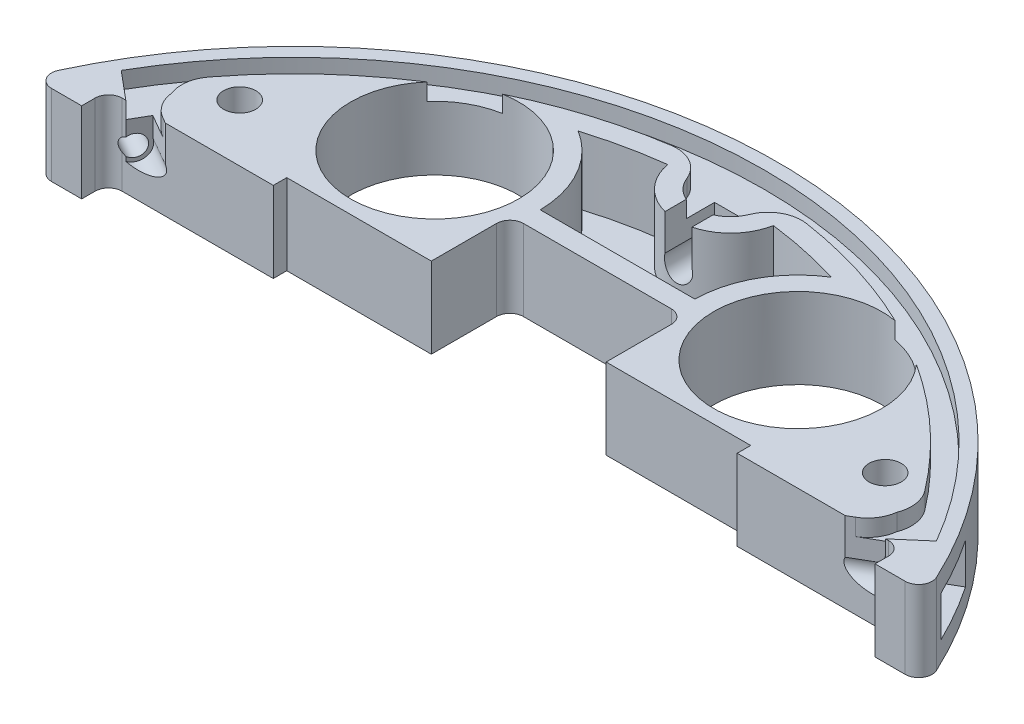
SolidWorks part; units mm, degrees
material "ABS"
ref_plane "Front Plane" through (0, 0, 0) normal (0, 0, 1) x (1, 0, 0)
ref_plane "Top Plane" through (0, 0, 0) normal (0, 1, 0) x (1, 0, 0)
ref_plane "Right Plane" through (0, 0, 0) normal (1, 0, 0) x (0, 0, -1)
sketch "Sketch1" plane through (0, 0, 0) normal (0, 1, 0) x (1, 0, 0)
  line L0 (0, -85) -> (-32.2211, -64.3879) construction
  line L1 (0, -85) -> (0, 0) construction
  arc A0 (36.2245, -62.2237) -> (-36.2245, -62.2237) centre (0, 0) ccw
  arc A1 (29.8119, -61.0352) -> (-29.8119, -61.0352) centre (0, -85) ccw
  arc A2 (36.2245, -62.2237) -> (29.8119, -61.0352) centre (33.7089, -57.9026) cw
  arc A3 (-29.8119, -61.0352) -> (-36.2245, -62.2237) centre (-33.7089, -57.9026) cw
  dimension "D1" = 144
  dimension "D2" = 76.5
  dimension "D4" = 5
  dimension "D3" = 85
extrude "Boss-Extrude1" add sketch "Sketch1" along normal mid plane 12
sketch "solenoid placement" plane through (0, 6, 0) normal (0, 1, 0) x (1, 0, 0)
  line L0 (0, 0) -> (0, -36) construction
  line L5 (-19, -36) -> (19, -36)
  line L7 (19, -36) -> (19, 28)
  line L9 (19, 28) -> (-19, 28)
  line L11 (-19, 28) -> (-19, -36)
  circle A1 centre (0, 0) radius 72 construction
  arc A2 (36.2245, -62.2237) -> (-36.2245, -62.2237) centre (0, 0) ccw construction
  dimension "D1" = 36
  dimension "D2" = 64
  dimension "D3" = 38
extrude "Cut-Extrude1" cut sketch "solenoid placement" against normal through all
sketch "Sketch4" plane through (0, 6, 0) normal (0, 1, 0) x (1, 0, 0)
  line L1 (-13, 28) -> (13, 28)
  line L2 (-13, 28) -> (-13, 43.2)
  line L4 (13, 28) -> (13, 43.2)
  line L5 (11, 45.2) -> (-11, 45.2)
  line L6 (19, 28) -> (-19, 28) construction
  arc A0 (11, 45.2) -> (13, 43.2) centre (11, 43.2) cw
  arc A1 (-11, 45.2) -> (-13, 43.2) centre (-11, 43.2) ccw
  point P6 (0, 28)
  dimension "D1" = 2
  dimension "D2" = 26
  dimension "D3" = 17.2
extrude "Cut-Extrude4" cut sketch "Sketch4" against normal through all
sketch "Sketch5" plane through (0, 6, 0) normal (0, 1, 0) x (1, 0, 0)
  line L0 (0, 0) -> (0, 72) construction
  arc A0 (36.2245, -62.2237) -> (-36.2245, -62.2237) centre (0, 0) ccw construction
  circle A1 centre (27, 48) radius 12.5
  circle A3 centre (-27, 48) radius 12.5
  dimension "D3" = 25
  dimension "D1" = 27
  dimension "D2" = 48
extrude "Cut-Extrude5" cut sketch "Sketch5" against normal through all
sketch "Sketch6" plane through (0, 6, 0) normal (0, 1, 0) x (1, 0, 0)
  line L0 (0, 0) -> (0, 72) construction
  arc A0 (36.2245, -62.2237) -> (-36.2245, -62.2237) centre (0, 0) ccw construction
  circle A1 centre (48, 40) radius 2.4
  circle A6 centre (-48, 40) radius 2.4
  dimension "D3" = 4.8
  dimension "D1" = 48
  dimension "D2" = 40
extrude "Cut-Extrude6" cut sketch "Sketch6" against normal through all
sketch "Sketch3" plane through (0, 6, 0) normal (0, 1, 0) x (1, 0, 0)
  line L1 (-72, -31.5) -> (72, -31.5) construction
  line L2 (-72, -31.5) -> (-72, 27.5)
  line L3 (-59, 31.5) -> (0, 31.5)
  line L4 (72, -31.5) -> (72, 27.5)
  line L5 (0, -31.5) -> (0, 31.5) construction
  line L6 (72, 27.5) -> (59, 27.5)
  line L9 (0, 31.5) -> (59, 31.5)
  line L10 (-72, -31.5) -> (-72, -101.6464)
  line L11 (72, -31.5) -> (72, -101.6464)
  line L12 (72, -101.6464) -> (-72, -101.6464)
  line L13 (59, 27.5) -> (59, 31.5)
  line L14 (-59, 27.5) -> (-59, 31.5)
  line L15 (-72, 27.5) -> (-59, 27.5)
  arc A0 (36.2245, -62.2237) -> (-36.2245, -62.2237) centre (0, 0) ccw construction
  point P0 (0, 0)
  dimension "D2" = 13
  dimension "D1" = 63
  dimension "D3" = 4
extrude "Cut-Extrude3" cut sketch "Sketch3" against normal through all
sketch "Sketch7" plane through (0, 0, 0) normal (0, 1, 0) x (1, 0, 0)
  line L0 (0, 0) -> (62.3538, 36) construction
  line L1 (0, 0) -> (-62.3538, 36) construction
  line L2 (0, 0) -> (0, 72) construction
  arc A0 (0, 72) -> (62.3538, 36) centre (0, 0) cw construction
  arc A1 (0, 72) -> (-62.3538, 36) centre (0, 0) ccw construction
  arc A2 (66.5413, 27.5) -> (-66.5413, 27.5) centre (0, 0) ccw construction
  dimension "D1" = 120
fillet "Fillet1" radius 2 4 edges at (-66.5413, 0, -27.5) (-59, 0, -31.5) (59, 0, -31.5) (66.5413, 0, -27.5)
sketch "Sketch8" plane through (0, 0, 0) normal (0, 1, 0) x (1, 0, 0)
  line L0 (5, 71.8262) -> (5, 68.8262)
  line L1 (0, 0) -> (64.7033, 31.583) construction
  line L2 (64.7033, 31.583) -> (59.7033, 40.2432) construction
  line L3 (64.7033, 31.583) -> (62.1052, 30.083)
  line L4 (62.1052, 30.083) -> (57.1052, 38.7432)
  line L5 (59.7033, 40.2432) -> (57.1052, 38.7432)
  line L6 (0, 0) -> (59.7033, 40.2432) construction
  line L7 (5, 68.8262) -> (-5, 68.8262)
  line L8 (-5, 71.8262) -> (-5, 68.8262)
  line L9 (5, 71.8262) -> (-5, 71.8262) construction
  line L10 (-59.7033, 40.2432) -> (-57.1052, 38.7432)
  line L11 (-57.1052, 38.7432) -> (-62.1052, 30.083)
  line L12 (-64.7033, 31.583) -> (-62.1052, 30.083)
  line L13 (-59.7033, 40.2432) -> (-64.7033, 31.583) construction
  arc A0 (59.7033, 40.2432) -> (64.7033, 31.583) centre (0, 0) cw
  arc A2 (-5, 71.8262) -> (5, 71.8262) centre (0, 0) cw
  arc A3 (-64.7033, 31.583) -> (-59.7033, 40.2432) centre (0, 0) cw
  point P4 (62.3538, 36)
  point P10 (-62.3538, 36)
  point P18 (0, 0)
  dimension "D1" = 10
  dimension "D2" = 3
extrude "Cut-Extrude7" cut sketch "Sketch8" against normal mid plane 6
sketch "Sketch10" plane through (0, 6, 0) normal (0, 1, 0) x (1, 0, 0)
  line L0 (0, 0) -> (0, 65) construction
  circle A0 centre (0, 65) radius 5
  dimension "D2" = 10
  dimension "D1" = 65
extrude "Cut-Extrude9" cut sketch "Sketch10" against normal blind 2.5
sketch "Sketch11" plane through (0, 6, 0) normal (0, 1, 0) x (1, 0, 0)
  line L1 (34.5, -33.5) -> (-34.5, -33.5)
  line L2 (34.5, -33.5) -> (34.5, 33.5)
  line L3 (34.5, 33.5) -> (-34.5, 33.5)
  line L4 (-34.5, -33.5) -> (-34.5, 33.5)
  line L5 (34.5, -33.5) -> (-34.5, 33.5) construction
  line L6 (34.5, 33.5) -> (-34.5, -33.5) construction
  point P0 (0, 0)
  dimension "D1" = 67
  dimension "D2" = 69
extrude "Cut-Extrude10" cut sketch "Sketch11" against normal through all
sketch "Sketch13" plane through (-59.6052, 0, -34.4131) normal (-0.866, 0, -0.5) x (-0.5, 0, 0.866)
  circle A0 centre (0, 0) radius 1.55
  dimension "D1" = 3.1
extrude "Cut-Extrude11" cut sketch "Sketch13" against normal blind 4.2
sketch "Sketch14" plane through (-55.9679, 0, -32.3131) normal (-0.866, 0, -0.5) x (-0.5, 0, 0.866)
  circle A0 centre (0, 0) radius 2.1
  dimension "D1" = 4.2
extrude "Cut-Extrude12" cut sketch "Sketch14" against normal blind 9
sketch "Sketch15" plane through (-55.9679, 0, -32.3131) normal (0.866, 0, 0.5) x (0.5, 0, -0.866)
  line L1 (-2, 0) -> (2, 0)
  line L2 (-2, 0) -> (-2, 10.8827)
  line L3 (-2, 10.8827) -> (2, 10.8827)
  line L4 (2, 0) -> (2, 10.8827)
  point P0 (0, 0)
  dimension "D1" = 4
extrude "Cut-Extrude13" cut sketch "Sketch15" along normal blind 9
pattern_circular "CirPattern1" count 3 over 120 about axis through (0, 6, 0) along (0, -1, 0) of "Cut-Extrude11", "Cut-Extrude12", "Cut-Extrude13"
sketch "Sketch16" plane through (0, 6, 0) normal (0, 1, 0) x (1, 0, 0)
  line L0 (0, 0) -> (-62.3538, 36) construction
  line L1 (0, 0) -> (62.3538, 36) construction
  line L2 (-56.4374, 31.5) -> (-54.9679, 34.0451) construction
  line L4 (-56.4374, 31.5) -> (-60.6218, 35)
  line L5 (3.5, 65) -> (-3.5, 65)
  line L6 (3.5, 65) -> (3.5, 66.9085)
  line L7 (-53.9374, 35.8301) -> (-55.6706, 37.2799)
  line L8 (-3.5, 65) -> (-3.5, 66.9085)
  line L9 (56.4775, 31.4305) -> (60.6218, 35)
  line L10 (53.9775, 35.7607) -> (55.6964, 37.2412)
  line L12 (54.9679, 34.0451) -> (56.4374, 31.5) construction
  line L13 (-53.9374, 35.8301) -> (-56.4374, 31.5)
  line L14 (53.9775, 35.7607) -> (56.4775, 31.4305)
  arc A0 (60.6218, 35) -> (-60.6218, 35) centre (0, 0) ccw
  arc A1 (55.6964, 37.2412) -> (3.5, 66.9085) centre (0, 0) ccw
  arc A2 (2, 60.4174) -> (-2, 60.4174) centre (0, 65) ccw construction
  arc A3 (-3.5, 66.9085) -> (-55.6706, 37.2799) centre (0, 0) ccw
  arc A4 (59, 29.5) -> (57, 31.5) centre (57, 29.5) ccw construction
  point P15 (0, 65)
  dimension "D1" = 3
  dimension "D2" = 140
  dimension "D3" = 7
  dimension "D4" = 5
  dimension "D5" = 5
extrude "Cut-Extrude14" cut sketch "Sketch16" against normal blind 2.5
fillet "Fillet2" radius 5 6 edges at (55.6964, 4.75, -37.2412) (-55.6706, 4.75, -37.2799) (54.9679, 4.75, -34.0451) (-54.9679, 4.75, -34.0451) (4.6497, 4.75, -66.8385) (-4.6497, 4.75, -66.8385)
sketch "Sketch17" plane through (0, 6, 0) normal (0, 1, 0) x (1, 0, 0)
  line L2 (11, 48.2) -> (-11, 48.2)
  line L3 (11.5013, 48.2) -> (-11.5013, 48.2)
  arc A2 (-38.6301, 58.2465) -> (-29.7173, 63.26) centre (-27, 48) ccw
  arc A3 (-11.5013, 48.2) -> (-18.8249, 61.1688) centre (-27, 48) ccw
  arc A5 (29.7173, 63.26) -> (38.6301, 58.2465) centre (27, 48) ccw
  arc A6 (18.8249, 61.1688) -> (11.5013, 48.2) centre (27, 48) ccw
  arc A8 (3.2, 57.6679) -> (7.4323, 62.04) centre (0, 65) ccw
  arc A9 (-7.861, 63.5154) -> (7.861, 63.5154) centre (0, 65) ccw
  arc A11 (-9.59, 63.2774) -> (-27.8843, 57.6061) centre (0, 0) ccw
  arc A12 (-7.861, 63.5154) -> (-18.8249, 61.1688) centre (0, 0) ccw
  arc A14 (27.8843, 57.6061) -> (9.59, 63.2774) centre (0, 0) ccw
  arc A15 (18.8249, 61.1688) -> (7.861, 63.5154) centre (0, 0) ccw
  dimension "D1" = 3
  dimension "D2" = 3
  dimension "D3" = 3
  dimension "D4" = 3
  dimension "D5" = 3
  dimension "D6" = 3
extrude "Cut-Extrude15" cut sketch "Sketch17" against normal blind 10
equation "\"smallPulleyTeeth\"= 30"
equation "\"largePulleyTeeth\"= 30"
equation "\"eighthThick\"= 3.0mm"
equation "\"sixteenthThick\" = 1.7mm"
equation "\"quarterThick\"=6.0mm"
equation "\"OD\" = 145mm"
equation "\"puckAngle\" = 60.5deg"
equation "\"puckDiam\" = 76.5mm"
equation "\"D2@Sketch1\"=\"puckDiam\""
equation "\"D1@Boss-Extrude1\"=\"eighthThick\"*4"
equation "\"axlePress\" = 5.9mm"
equation "\"press\" = 0.2mm"
equation "\"wheelClear\" = 0.3mm"
equation "\"10-32clear\" = 4.8mm"
equation "\"6-32clear\" = 3.3mm"
equation "\"8-32clear\" = 4.0mm"
equation "\"wheelHeight\" = 22mm"
equation "\"wheelWell\" = 65mm"
equation "\"puckDist\" = 85mm"
equation "\"scoopFillet\" = 5mm"
equation "\"4-40clear\" = 3.0mm"
equation "\"D3@Sketch1\"=\"puckDist\""
equation "\"D4@Sketch1\"=\"scoopFillet\""
equation "\"D3@Sketch6\"=\"10-32clear\""
equation "\"D2@Sketch8\"=\"eighthThick\""
equation "\"10-32tap\" = 4.45mm"
equation "\"ledSmall\" = 3.1mm"
equation "\"ledLarge\" = 4.2mm"
equation "\"ledLength\" = 4.2mm"
equation "\"D1@Sketch13\"=\"ledSmall\""
equation "\"D1@Cut-Extrude11\"=\"ledLength\""
equation "\"D1@Sketch14\"=\"ledLarge\""
